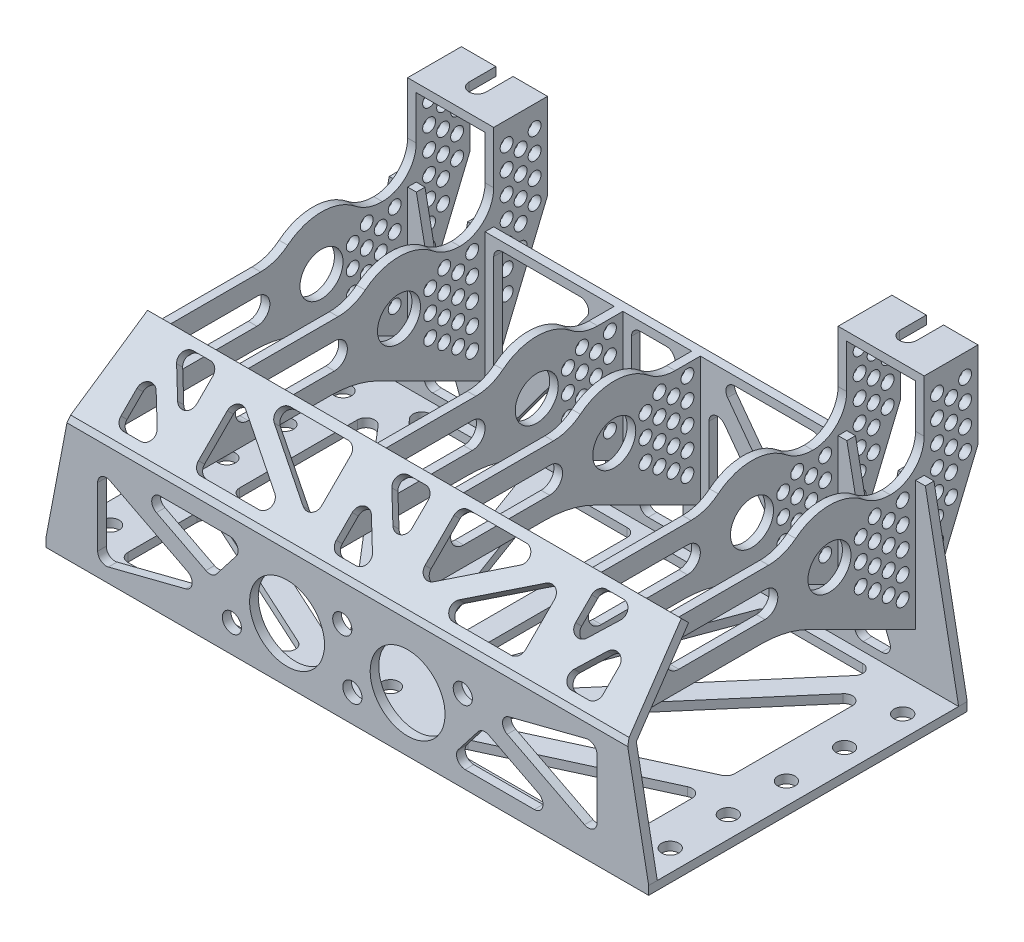
SolidWorks part; units mm, degrees
material "AISI 4340 Steel, normalized"
ref_plane "Front Plane" through (0, 0, 0) normal (0, 0, 1) x (1, 0, 0)
ref_plane "Top Plane" through (0, 0, 0) normal (0, 1, 0) x (1, 0, 0)
ref_plane "Right Plane" through (0, 0, 0) normal (1, 0, 0) x (0, 0, -1)
sketch "Sketch1" plane through (0, 0, 0) normal (1, 0, 0) x (0, 0, -1)
  line L0 (40, 15) -> (28.2843, 15)
  line L1 (-100, 15) -> (-100, -15)
  line L2 (-100, -15) -> (-31.8034, -15)
  line L3 (40, -15) -> (40, 15)
  line L4 (-28.2843, 15) -> (-100, 15)
  line L5 (-20, 15) -> (20, 15) construction
  line L6 (-9.4427, -20.2786) -> (40, -45)
  line L7 (40, -45) -> (40, -15)
  line L8 (-20, -15) -> (40, -15) construction
  line L9 (0, 0) -> (-100, 0) construction
  line L10 (-30, 0) -> (-60, 0) construction
  line L11 (-30, -6) -> (-60, -6)
  line L12 (-30, 6) -> (-60, 6)
  circle A0 centre (0, 0) radius 10
  arc A1 (-15.7135, 19.4444) -> (15.7135, 19.4444) centre (0, 0) cw
  arc A2 (15.7135, 19.4444) -> (28.2843, 15) centre (28.2843, 35) ccw
  arc A3 (-15.7135, 19.4444) -> (-28.2843, 15) centre (-28.2843, 35) cw
  arc A4 (-9.4427, -20.2786) -> (-31.8034, -15) centre (-31.8034, -65) ccw
  arc A5 (-30, -6) -> (-30, 6) centre (-30, 0) ccw
  arc A6 (-60, 6) -> (-60, -6) centre (-60, 0) ccw
  point P23 (-45, 0)
  dimension "D1" = 20
  dimension "D2" = 140
  dimension "D6" = 25
  dimension "D7" = 20
  dimension "D10" = 50
  dimension "D3" = 30
  dimension "D4" = 15
  dimension "D5" = 100
  dimension "D8" = 30
  dimension "D9" = 60
  dimension "D11" = 12
  dimension "D12" = 60
  dimension "D13" = 30
extrude "Boss-Extrude1" add sketch "Sketch1" along normal blind 4 from offset 16
mirror "Mirror1" about plane through (0, 0, 0) normal (1, 0, 0) of bodies 101
sketch "Sketch2" plane through (0, 0, 100) normal (0, 0, 1) x (1, 0, 0)
  line L0 (-140, 15) -> (140, 15)
  line L1 (140, 15) -> (140, -70)
  line L2 (140, -70) -> (-140, -70)
  line L3 (-140, -70) -> (-140, 15)
  dimension "D1" = 85
  dimension "D2" = 280
  dimension "D3" = 140
  dimension "D4" = 70
extrude "Boss-Extrude2" add sketch "Sketch2" along normal blind 4
sketch "Sketch3" plane through (0, 0, 104) normal (0, 0, 1) x (1, 0, 0)
  line L0 (0, 0) -> (0, -70) construction
  line L1 (-140, -70) -> (140, -70) construction
  circle A0 centre (-28, -44.5) radius 17.4
  circle A1 centre (28, -44.5) radius 17.4
  dimension "D4" = 34.8
  dimension "D5" = 28
  dimension "D6" = 44.5
extrude "Cut-Extrude1" cut sketch "Sketch3" against normal blind 10
sketch "Sketch4" plane through (0, 0, 104) normal (0, 0, 1) x (1, 0, 0)
  line L0 (-53.6437, -57.05) -> (-2.3563, -31.95) construction
  line L1 (2.3563, -57.05) -> (53.6437, -31.95) construction
  line L2 (0, 0) -> (0, -70) construction
  line L3 (-140, -70) -> (140, -70) construction
  line L4 (-28, -44.5) -> (28, -44.5) construction
  circle A8 centre (28, -44.5) radius 17.4 construction
  circle A9 centre (-28, -44.5) radius 17.4 construction
  circle A10 centre (28, -44.5) radius 17.4
  circle A11 centre (-28, -44.5) radius 17.4
  circle A12 centre (-28, -44.5) radius 28.55 construction
  circle A13 centre (28, -44.5) radius 28.55 construction
  circle A14 centre (-53.6437, -57.05) radius 4.45
  circle A15 centre (-2.3563, -31.95) radius 4.45
  circle A16 centre (2.3563, -57.05) radius 4.45
  circle A17 centre (53.6437, -31.95) radius 4.45
  dimension "D2" = 57.1
  dimension "D3" = 8.9
  dimension "D1" = 26.077
extrude "Cut-Extrude2" cut sketch "Sketch4" against normal blind 10
pattern_linear "LPattern2" count 2 spacing 64 along (1, 0, 0) count 2 spacing 100 along (-1, 0, 0) of "Boss-Extrude1"
sketch "Sketch5" plane through (84, 0, 0) normal (1, 0, 0) x (0, 0, -1)
  line L0 (-60, -6) -> (-30, -6) construction
  line L1 (-60, -6) -> (-30, -6)
  line L2 (-30, 6) -> (-60, 6) construction
  line L3 (-30, 6) -> (-60, 6)
  line L4 (40, -45) -> (40, 15)
  line L5 (40, 15) -> (28.2843, 15)
  line L6 (-100, 15) -> (-100, -15)
  line L7 (-100, -15) -> (-31.8034, -15)
  line L8 (40, -45) -> (40, 15)
  line L10 (-100, 15) -> (-100, -15)
  line L11 (-100, -15) -> (-31.8034, -15)
  line L14 (40, 15) -> (28.2843, 15)
  line L15 (-28.2843, 15) -> (-100, 15)
  line L16 (-28.2843, 15) -> (-100, 15)
  line L17 (-9.4427, -20.2786) -> (40, -45)
  line L18 (-9.4427, -20.2786) -> (40, -45)
  circle A0 centre (0, 0) radius 10 construction
  circle A1 centre (0, 0) radius 10
  arc A2 (-60, 6) -> (-60, -6) centre (-60, 0) ccw construction
  arc A3 (-30, -6) -> (-30, 6) centre (-30, 0) ccw construction
  arc A4 (-60, 6) -> (-60, -6) centre (-60, 0) ccw
  arc A5 (15.7135, 19.4444) -> (28.2843, 15) centre (28.2843, 35) ccw
  arc A6 (15.7135, 19.4444) -> (28.2843, 15) centre (28.2843, 35) ccw
  arc A7 (15.7135, 19.4444) -> (-15.7135, 19.4444) centre (0, 0) ccw
  arc A8 (15.7135, 19.4444) -> (-15.7135, 19.4444) centre (0, 0) ccw
  arc A9 (-28.2843, 15) -> (-15.7135, 19.4444) centre (-28.2843, 35) ccw
  arc A10 (-28.2843, 15) -> (-15.7135, 19.4444) centre (-28.2843, 35) ccw
  arc A11 (-30, -6) -> (-30, 6) centre (-30, 0) ccw
  arc A12 (-9.4427, -20.2786) -> (-31.8034, -15) centre (-31.8034, -65) ccw
  arc A13 (-9.4427, -20.2786) -> (-31.8034, -15) centre (-31.8034, -65) ccw
  dimension "D1" = 0
extrude "Boss-Extrude3" add sketch "Sketch5" along normal blind 4 from offset 32
sketch "Sketch6" plane through (-84, 0, 0) normal (-1, 0, 0) x (0, 0, 1)
  line L0 (30, 6) -> (60, 6) construction
  line L1 (60, -6) -> (30, -6) construction
  line L2 (30, 6) -> (60, 6)
  line L3 (60, -6) -> (30, -6)
  line L4 (-40, 15) -> (-40, -45)
  line L5 (31.8034, -15) -> (100, -15)
  line L6 (100, -15) -> (100, 15)
  line L7 (-28.2843, 15) -> (-40, 15)
  line L8 (-40, 15) -> (-40, -45)
  line L9 (31.8034, -15) -> (100, -15)
  line L10 (100, -15) -> (100, 15)
  line L11 (-28.2843, 15) -> (-40, 15)
  line L14 (-40, -45) -> (9.4427, -20.2786)
  line L15 (-40, -45) -> (9.4427, -20.2786)
  line L16 (100, 15) -> (28.2843, 15)
  line L17 (100, 15) -> (28.2843, 15)
  circle A0 centre (0, 0) radius 10 construction
  circle A1 centre (0, 0) radius 10
  arc A2 (30, 6) -> (30, -6) centre (30, 0) ccw construction
  arc A3 (60, -6) -> (60, 6) centre (60, 0) ccw construction
  arc A4 (30, 6) -> (30, -6) centre (30, 0) ccw
  arc A5 (15.7135, 19.4444) -> (28.2843, 15) centre (28.2843, 35) ccw
  arc A6 (15.7135, 19.4444) -> (28.2843, 15) centre (28.2843, 35) ccw
  arc A7 (15.7135, 19.4444) -> (-15.7135, 19.4444) centre (0, 0) ccw
  arc A8 (15.7135, 19.4444) -> (-15.7135, 19.4444) centre (0, 0) ccw
  arc A9 (-28.2843, 15) -> (-15.7135, 19.4444) centre (-28.2843, 35) ccw
  arc A10 (-28.2843, 15) -> (-15.7135, 19.4444) centre (-28.2843, 35) ccw
  arc A11 (60, -6) -> (60, 6) centre (60, 0) ccw
  arc A12 (31.8034, -15) -> (9.4427, -20.2786) centre (31.8034, -65) ccw
  arc A13 (31.8034, -15) -> (9.4427, -20.2786) centre (31.8034, -65) ccw
  dimension "D1" = 0
extrude "Boss-Extrude4" add sketch "Sketch6" along normal blind 4 from offset 32
sketch "Sketch7" plane through (0, 0, 0) normal (1, 0, 0) x (0, 0, -1)
  line L0 (-100, -15) -> (-70, 15)
  line L2 (-100, -15) -> (-31.8034, -15) construction
  line L3 (-70, 15) -> (-68.8914, 31.7021)
  line L4 (-68.8914, 31.7021) -> (-121.4755, 31.7021)
  line L5 (-121.4755, 31.7021) -> (-121.4755, -15)
  line L6 (-121.4755, -15) -> (-100, -15)
  line L7 (-28.2843, 15) -> (-100, 15) construction
  dimension "D1" = 45
extrude "Cut-Extrude3" cut sketch "Sketch7" against normal through all both and the other way through all
sketch "Sketch8" plane through (0, 0, 0) normal (1, 0, 0) x (0, 0, -1)
  line L0 (-100, -15) -> (-70, 15)
  line L1 (-102.8284, -12.1716) -> (-72.8284, 17.8284)
  line L2 (-100, -15) -> (-102.8284, -12.1716) construction
  line L3 (-72.8284, 17.8284) -> (-70, 15)
  line L4 (-104, -15) -> (-102.8284, -12.1716)
  line L5 (-100, -15) -> (-104, -15)
  line L6 (-28.2843, 15) -> (-70, 15) construction
  dimension "D1" = 4
extrude "Boss-Extrude5" add sketch "Sketch8" along normal mid plane 280
sketch "Sketch9" plane through (0, 0, -40) normal (0, 0, -1) x (-1, 0, 0)
  line L1 (-140, -70) -> (140, -70)
  line L2 (-140, -70) -> (-140, 15)
  line L3 (-140, 15) -> (140, 15)
  line L4 (140, -70) -> (140, 15)
  line L5 (0, 15) -> (0, -70) construction
  line L6 (-140, -27.5) -> (140, -27.5) construction
  point P0 (0, -27.5)
  dimension "D1" = 280
  dimension "D2" = 85
  dimension "D3" = 27.5
extrude "Boss-Extrude6" add sketch "Sketch9" along normal blind 4
sketch "Sketch10" plane through (0, -70, 0) normal (0, -1, 0) x (1, 0, 0)
  line L1 (-140, 104) -> (140, 104)
  line L2 (-140, 104) -> (-140, -44)
  line L3 (-140, -44) -> (140, -44)
  line L4 (140, 104) -> (140, -44)
extrude "Boss-Extrude7" add sketch "Sketch10" against normal blind 4
sketch "Sketch11" plane through (0, 45.3284, 45.3284) normal (0, 0.7071, 0.7071) x (1, 0, 0)
  line L0 (-140, -60.1041) -> (140, -60.1041) construction
  line L1 (-140, -38.8909) -> (-140, -81.3173) construction
  line L2 (140, -38.8909) -> (140, -81.3173) construction
  line L3 (0, -38.8909) -> (0, -81.3173) construction
  line L4 (140, -38.8909) -> (-140, -38.8909) construction
  line L5 (140, -81.3173) -> (-140, -81.3173) construction
  line L6 (-80, -38.8909) -> (-20, -81.3173) construction
  line L7 (-20, -81.3173) -> (-20, -38.8909) construction
  line L8 (-20, -9.3934) -> (-20, -38.8909) construction
  line L12 (-80, -38.8909) -> (-80, -81.3173) construction
  line L13 (-80, -81.3173) -> (-20, -81.3173) construction
  line L14 (-69.6906, -51.0797) -> (-42.8607, -70.0513)
  line L15 (-72, -77.3173) -> (-45.1701, -77.3173)
  line L16 (-76, -54.3457) -> (-76, -73.3173)
  line L17 (-80, -38.8909) -> (-20, -38.8909) construction
  line L18 (-57.1393, -50.1569) -> (-30.3094, -69.1285)
  line L19 (-24, -65.8625) -> (-24, -46.8909)
  line L20 (-54.8299, -42.8909) -> (-28, -42.8909)
  line L21 (-67.4149, -42.8909) -> (-24, -73.5899) construction
  line L22 (-67.4149, -42.8909) -> (-24, -42.8909) construction
  line L23 (-24, -73.5899) -> (-24, -42.8909) construction
  line L24 (-76, -46.6183) -> (-32.5851, -77.3173) construction
  line L25 (-76, -77.3173) -> (-32.5851, -77.3173) construction
  line L26 (-76, -46.6183) -> (-76, -77.3173) construction
  line L27 (76, -54.3457) -> (76, -73.3173)
  line L28 (69.6906, -51.0797) -> (42.8607, -70.0513)
  line L29 (72, -77.3173) -> (45.1701, -77.3173)
  line L30 (57.1393, -50.1569) -> (30.3094, -69.1285)
  line L31 (54.8299, -42.8909) -> (28, -42.8909)
  line L32 (24, -65.8625) -> (24, -46.8909)
  line L33 (-84, -38.8909) -> (-84, -81.3173) construction
  line L34 (-84, -81.3173) -> (-116, -38.8909) construction
  line L35 (-116, -38.8909) -> (-116, -81.3173) construction
  line L36 (-116, -81.3173) -> (-84, -81.3173) construction
  line L37 (-116, -38.8909) -> (-84, -38.8909) construction
  line L38 (-112, -62.7828) -> (-112, -73.3173)
  line L39 (-108, -77.3173) -> (-100.0544, -77.3173)
  line L40 (-96.8609, -70.9086) -> (-104.8065, -60.3741)
  line L41 (-88, -46.8909) -> (-88, -57.4253)
  line L42 (-95.1935, -59.834) -> (-103.1391, -49.2995)
  line L43 (-99.9456, -42.8909) -> (-92, -42.8909)
  line L44 (-112, -50.8368) -> (-112, -77.3173) construction
  line L45 (-112, -77.3173) -> (-92.0272, -77.3173) construction
  line L46 (-92.0272, -77.3173) -> (-112, -50.8368) construction
  line L47 (-88, -42.8909) -> (-88, -69.3713) construction
  line L48 (-88, -69.3713) -> (-107.9728, -42.8909) construction
  line L49 (-107.9728, -42.8909) -> (-88, -42.8909) construction
  line L50 (96.8609, -70.9086) -> (104.8065, -60.3741)
  line L51 (108, -77.3173) -> (100.0544, -77.3173)
  line L52 (112, -62.7828) -> (112, -73.3173)
  line L53 (95.1935, -59.834) -> (103.1391, -49.2995)
  line L54 (99.9456, -42.8909) -> (92, -42.8909)
  line L55 (88, -46.8909) -> (88, -57.4253)
  line L56 (12, -46.8909) -> (12, -57.4253)
  line L57 (4.8065, -59.834) -> (-3.1391, -49.2995)
  line L58 (0.0544, -42.8909) -> (8, -42.8909)
  line L59 (-12, -62.7828) -> (-12, -73.3173)
  line L60 (-8, -77.3173) -> (-0.0544, -77.3173)
  line L61 (3.1391, -70.9086) -> (-4.8065, -60.3741)
  arc A0 (-57.1393, -50.1569) -> (-54.8299, -42.8909) centre (-54.8299, -46.8909) cw
  arc A1 (-24, -46.8909) -> (-28, -42.8909) centre (-28, -46.8909) ccw
  arc A2 (-30.3094, -69.1285) -> (-24, -65.8625) centre (-28, -65.8625) ccw
  arc A3 (-42.8607, -70.0513) -> (-45.1701, -77.3173) centre (-45.1701, -73.3173) cw
  arc A4 (-72, -77.3173) -> (-76, -73.3173) centre (-72, -73.3173) cw
  arc A5 (-69.6906, -51.0797) -> (-76, -54.3457) centre (-72, -54.3457) ccw
  arc A6 (72, -77.3173) -> (76, -73.3173) centre (72, -73.3173) ccw
  arc A7 (69.6906, -51.0797) -> (76, -54.3457) centre (72, -54.3457) cw
  arc A8 (42.8607, -70.0513) -> (45.1701, -77.3173) centre (45.1701, -73.3173) ccw
  arc A9 (30.3094, -69.1285) -> (24, -65.8625) centre (28, -65.8625) cw
  arc A10 (57.1393, -50.1569) -> (54.8299, -42.8909) centre (54.8299, -46.8909) ccw
  arc A11 (24, -46.8909) -> (28, -42.8909) centre (28, -46.8909) cw
  arc A12 (-112, -73.3173) -> (-108, -77.3173) centre (-108, -73.3173) ccw
  arc A13 (-112, -62.7828) -> (-104.8065, -60.3741) centre (-108, -62.7828) cw
  arc A14 (-100.0544, -77.3173) -> (-96.8609, -70.9086) centre (-100.0544, -73.3173) ccw
  arc A15 (-88, -57.4253) -> (-95.1935, -59.834) centre (-92, -57.4253) cw
  arc A16 (-88, -46.8909) -> (-92, -42.8909) centre (-92, -46.8909) ccw
  arc A17 (-103.1391, -49.2995) -> (-99.9456, -42.8909) centre (-99.9456, -46.8909) cw
  arc A18 (100.0544, -77.3173) -> (96.8609, -70.9086) centre (100.0544, -73.3173) cw
  arc A19 (112, -73.3173) -> (108, -77.3173) centre (108, -73.3173) cw
  arc A20 (112, -62.7828) -> (104.8065, -60.3741) centre (108, -62.7828) ccw
  arc A21 (88, -57.4253) -> (95.1935, -59.834) centre (92, -57.4253) ccw
  arc A22 (103.1391, -49.2995) -> (99.9456, -42.8909) centre (99.9456, -46.8909) ccw
  arc A23 (88, -46.8909) -> (92, -42.8909) centre (92, -46.8909) cw
  arc A24 (12, -46.8909) -> (8, -42.8909) centre (8, -46.8909) ccw
  arc A25 (12, -57.4253) -> (4.8065, -59.834) centre (8, -57.4253) cw
  arc A26 (-3.1391, -49.2995) -> (0.0544, -42.8909) centre (0.0544, -46.8909) cw
  arc A27 (-12, -62.7828) -> (-4.8065, -60.3741) centre (-8, -62.7828) cw
  arc A28 (-12, -73.3173) -> (-8, -77.3173) centre (-8, -73.3173) ccw
  arc A29 (-0.0544, -77.3173) -> (3.1391, -70.9086) centre (-0.0544, -73.3173) ccw
  dimension "D3" = 4
  dimension "D6" = 4
  dimension "D1" = 4
  dimension "D2" = 4
  dimension "D4" = 4
  dimension "D5" = 4
  dimension "D7" = 2
extrude "Cut-Extrude4" cut sketch "Sketch11" against normal blind 4
sketch "Sketch12" plane through (0, 0, 104) normal (0, 0, 1) x (1, 0, 0)
  line L0 (0, -70) -> (0, 0) construction
  line L1 (-140, -70) -> (140, -70) construction
  line L2 (120, -15) -> (120, -66) construction
  line L3 (140, -66) -> (-140, -66) construction
  line L6 (61.655, -36.0609) -> (38.3935, -66) construction
  line L8 (42.5693, -55.8198) -> (58.3027, -35.5699) construction
  line L9 (120, -66) -> (61.655, -36.0609) construction
  line L19 (120, -70) -> (35.2856, -70) construction
  line L20 (53.6437, -31.95) -> (120, -15) construction
  line L21 (0, -43.705) -> (-140, -42.5) construction
  line L22 (-140, -15) -> (-140, -70) construction
  line L33 (140, -15) -> (-140, -15) construction
  line L37 (110.1738, -56.4619) -> (74.2598, -38.033)
  line L38 (75.096, -30.5987) -> (111.01, -21.4248)
  line L39 (116, -25.3004) -> (116, -52.9031)
  line L40 (120, -66) -> (53.6437, -31.95) construction
  line L41 (0, -66) -> (-140, -66) construction
  line L42 (86.8866, -62) -> (54.7401, -62)
  line L49 (120, -66) -> (38.3935, -66) construction
  line L50 (60.7446, -43.7522) -> (51.5814, -55.5458)
  line L51 (88.7128, -54.4412) -> (65.7295, -42.6476)
  line L52 (116, -59.4516) -> (64.8648, -33.2121) construction
  line L53 (116, -20.1502) -> (116, -59.4516) construction
  line L54 (64.8648, -33.2121) -> (116, -20.1502) construction
  line L55 (103.4433, -62) -> (46.5668, -62) construction
  line L56 (103.4433, -62) -> (62.7792, -41.1336) construction
  line L57 (62.7792, -41.1336) -> (46.5668, -62) construction
  line L58 (-86.8866, -22.8083) -> (-54.7401, -22.8083)
  line L59 (-60.7446, -41.0561) -> (-51.5814, -29.2624)
  line L60 (-88.7128, -30.3671) -> (-65.7295, -42.1607)
  line L61 (-110.1738, -28.3463) -> (-74.2598, -46.7752)
  line L62 (-75.096, -54.2096) -> (-111.01, -63.3834)
  line L63 (-116, -59.5079) -> (-116, -31.9052)
  arc A25 (110.1738, -56.4619) -> (116, -52.9031) centre (112, -52.9031) ccw
  arc A26 (111.01, -21.4248) -> (116, -25.3004) centre (112, -25.3004) cw
  arc A27 (86.8866, -62) -> (88.7128, -54.4412) centre (86.8866, -58) ccw
  arc A28 (60.7446, -43.7522) -> (65.7295, -42.6476) centre (63.9033, -46.2064) cw
  arc A29 (54.7401, -62) -> (51.5814, -55.5458) centre (54.7401, -58) cw
  arc A30 (74.2598, -38.033) -> (75.096, -30.5987) centre (76.086, -34.4742) cw
  arc A31 (-54.7401, -22.8083) -> (-51.5814, -29.2624) centre (-54.7401, -26.8083) cw
  arc A32 (-86.8866, -22.8083) -> (-88.7128, -30.3671) centre (-86.8866, -26.8083) ccw
  arc A33 (-60.7446, -41.0561) -> (-65.7295, -42.1607) centre (-63.9033, -38.6019) cw
  arc A34 (-74.2598, -46.7752) -> (-75.096, -54.2096) centre (-76.086, -50.334) cw
  arc A35 (-110.1738, -28.3463) -> (-116, -31.9052) centre (-112, -31.9052) ccw
  arc A36 (-111.01, -63.3834) -> (-116, -59.5079) centre (-112, -59.5079) cw
  point P62 (0, -42.775)
  point P69 (0, -42.4041)
  point P70 (0, -42.775)
  dimension "D5" = 2
  dimension "D4" = 4
  dimension "D3" = 4
  dimension "D1" = 35.2856
  dimension "D2" = 4
extrude "Cut-Extrude5" cut sketch "Sketch12" against normal blind 4
sketch "Sketch13" plane through (0, 0, -44) normal (0, 0, -1) x (-1, 0, 0)
  line L0 (0, 15) -> (0, -70) construction
  line L3 (-16, 15) -> (16, 15) construction
  line L4 (-140, -70) -> (140, -70) construction
  line L5 (-116, 15) -> (-116, -66) construction
  line L7 (-16, -66) -> (16, -66) construction
  line L8 (-84, 15) -> (-84, -66) construction
  line L9 (140, 15) -> (-140, 15) construction
  line L10 (-116, 15) -> (-84, 15) construction
  line L11 (-84, -66) -> (-116, 15) construction
  line L12 (-116, 15) -> (-84, 15) construction
  line L13 (-84, -66) -> (-116, -66) construction
  line L14 (-80, -66) -> (-20, -66) construction
  line L27 (-80, 15) -> (-80, -66) construction
  line L28 (-84, 15) -> (-80, 15) construction
  line L29 (-80, -66) -> (-20, 15) construction
  line L30 (-20, 15) -> (-20, -66) construction
  line L31 (-80, 15) -> (-20, 15) construction
  line L32 (-16, 15) -> (-16, -66) construction
  line L34 (-16, 15) -> (16, 15) construction
  line L35 (16, 15) -> (16, -66) construction
  line L36 (16, -66) -> (-16, 15) construction
  line L39 (-76, 7) -> (-76, -41.7598)
  line L40 (-68.7858, -44.1407) -> (-32.6674, 4.6191)
  line L41 (-72, 11) -> (-35.8817, 11)
  line L42 (-67.3326, -55.6191) -> (-31.2142, -6.8593)
  line L43 (-24, -9.2402) -> (-24, -58)
  line L44 (-64.1183, -62) -> (-28, -62)
  line L45 (-12, -27.023) -> (-12, -58)
  line L46 (-8, -62) -> (4.2378, -62)
  line L47 (7.958, -56.5303) -> (-4.2798, -25.5533)
  line L48 (4.2798, -25.4467) -> (-7.958, 5.5303)
  line L49 (-4.2378, 11) -> (8, 11)
  line L50 (12, 7) -> (12, -23.977)
  line L51 (-10.1189, 11) -> (12, 11) construction
  line L52 (12, 11) -> (12, -44.9885) construction
  line L53 (12, -44.9885) -> (-10.1189, 11) construction
  line L54 (-12, -62) -> (10.1189, -62) construction
  line L55 (10.1189, -62) -> (-12, -6.0115) construction
  line L56 (-12, -6.0115) -> (-12, -62) construction
  line L57 (-72.0592, -62) -> (-24, 2.8799) construction
  line L58 (-24, 2.8799) -> (-24, -62) construction
  line L59 (-72.0592, -62) -> (-24, -62) construction
  line L60 (-76, 11) -> (-76, -53.8799) construction
  line L61 (-76, -53.8799) -> (-27.9408, 11) construction
  line L62 (-76, 11) -> (-27.9408, 11) construction
  line L69 (80, 15) -> (20, 15) construction
  line L70 (20, 15) -> (20, -66) construction
  line L71 (80, -66) -> (20, 15) construction
  line L72 (80, 15) -> (80, -66) construction
  line L73 (80, -66) -> (20, -66) construction
  line L74 (84, -66) -> (116, -66) construction
  line L75 (116, 15) -> (84, 15) construction
  line L76 (84, -66) -> (116, 15) construction
  line L77 (84, 15) -> (84, -66) construction
  line L78 (116, 15) -> (116, -66) construction
  line L79 (64.1183, -62) -> (28, -62)
  line L80 (24, -9.2402) -> (24, -58)
  line L81 (67.3326, -55.6191) -> (31.2142, -6.8593)
  line L82 (72, 11) -> (35.8817, 11)
  line L83 (68.7858, -44.1407) -> (32.6674, 4.6191)
  line L84 (76, 7) -> (76, -41.7598)
  arc A0 (8, 11) -> (12, 7) centre (8, 7) cw
  arc A1 (-7.958, 5.5303) -> (-4.2378, 11) centre (-4.2378, 7) cw
  arc A2 (4.2798, -25.4467) -> (12, -23.977) centre (8, -23.977) ccw
  arc A3 (4.2378, -62) -> (7.958, -56.5303) centre (4.2378, -58) ccw
  arc A4 (-12, -58) -> (-8, -62) centre (-8, -58) ccw
  arc A5 (-12, -27.023) -> (-4.2798, -25.5533) centre (-8, -27.023) cw
  arc A6 (-31.2142, -6.8593) -> (-24, -9.2402) centre (-28, -9.2402) cw
  arc A7 (-24, -58) -> (-28, -62) centre (-28, -58) cw
  arc A8 (-67.3326, -55.6191) -> (-64.1183, -62) centre (-64.1183, -58) ccw
  arc A9 (-76, -41.7598) -> (-68.7858, -44.1407) centre (-72, -41.7598) ccw
  arc A10 (-32.6674, 4.6191) -> (-35.8817, 11) centre (-35.8817, 7) ccw
  arc A11 (-76, 7) -> (-72, 11) centre (-72, 7) cw
  arc A24 (76, 7) -> (72, 11) centre (72, 7) ccw
  arc A25 (32.6674, 4.6191) -> (35.8817, 11) centre (35.8817, 7) cw
  arc A26 (76, -41.7598) -> (68.7858, -44.1407) centre (72, -41.7598) cw
  arc A27 (67.3326, -55.6191) -> (64.1183, -62) centre (64.1183, -58) cw
  arc A28 (24, -58) -> (28, -62) centre (28, -58) ccw
  arc A29 (31.2142, -6.8593) -> (24, -9.2402) centre (28, -9.2402) ccw
  dimension "D5" = 4
  dimension "D8" = 4
  dimension "D1" = 4
  dimension "D4" = 4
  dimension "D6" = 4
  dimension "D7" = 4
extrude "Cut-Extrude6" cut sketch "Sketch13" against normal blind 4
sketch "Sketch14" plane through (0, -70, 0) normal (0, -1, 0) x (1, 0, 0)
  line L0 (0, -40) -> (0, 100) construction
  line L1 (-5, -31) -> (-5, 55.3142)
  line L2 (-10.8137, 56.355) -> (-42.6139, -29.6123)
  line L3 (-51.7876, -40) -> (0, -40) construction
  line L4 (-38.8624, -35) -> (-9, -35)
  line L6 (-120, 44.8095) -> (-120, 100) construction
  line L7 (-120, 100) -> (0, 100) construction
  line L8 (140, 100) -> (-140, 100) construction
  line L9 (-120, -40) -> (0, 100) construction
  line L10 (0, 100) -> (-120, 44.8095) construction
  line L11 (0, 100) -> (-51.7876, -40) construction
  line L23 (-39.4362, 87.3659) -> (-109.3286, 55.2209)
  line L24 (-120, 44.8095) -> (-120, -40) construction
  line L25 (-120, -40) -> (-51.7876, -40) construction
  line L26 (-115, 58.855) -> (-115, 91)
  line L27 (-111, 95) -> (-41.1076, 95)
  line L28 (-107.963, -18.2738) -> (-30.5473, 72.0444)
  line L29 (-35.2557, 78.2817) -> (-112.6714, 42.6766)
  line L30 (-115, 39.0425) -> (-115, -15.6707)
  line L31 (-20.1915, 59.8271) -> (-54.3028, -32.3877)
  line L32 (-100.432, -35) -> (-58.0544, -35)
  line L33 (-103.469, -28.3968) -> (-25.283, 62.8202)
  line L34 (-115, -26.4837) -> (-18.658, 85.9153) construction
  line L35 (-18.658, 85.9153) -> (-115, 41.6056) construction
  line L36 (-22.8375, 95) -> (-115, 52.6125) construction
  line L37 (-115, 95) -> (-22.8375, 95) construction
  line L38 (-5, -35) -> (-5, 72.0713) construction
  line L39 (-5, 72.0713) -> (-44.6069, -35) construction
  line L40 (-14.3783, 75.5424) -> (-55.2691, -35) construction
  line L41 (-109.1289, -35) -> (-14.3783, 75.5424) construction
  line L42 (-44.6069, -35) -> (-5, -35) construction
  line L43 (-109.1289, -35) -> (-55.2691, -35) construction
  line L44 (-115, 41.6056) -> (-115, -26.4837) construction
  line L45 (-115, 52.6125) -> (-115, 95) construction
  line L46 (38.8624, -35) -> (9, -35)
  line L47 (10.8137, 56.355) -> (42.6139, -29.6123)
  line L48 (5, -31) -> (5, 55.3142)
  line L49 (103.469, -28.3968) -> (25.283, 62.8202)
  line L50 (100.432, -35) -> (58.0544, -35)
  line L51 (20.1915, 59.8271) -> (54.3028, -32.3877)
  line L52 (115, 39.0425) -> (115, -15.6707)
  line L53 (35.2557, 78.2817) -> (112.6714, 42.6766)
  line L54 (107.963, -18.2738) -> (30.5473, 72.0444)
  line L55 (111, 95) -> (41.1076, 95)
  line L56 (115, 58.855) -> (115, 91)
  line L57 (39.4362, 87.3659) -> (109.3286, 55.2209)
  line L58 (-130, 104) -> (-130, -44) construction
  line L59 (-140, 104) -> (140, 104) construction
  line L60 (140, -44) -> (-140, -44) construction
  line L61 (130, 104) -> (130, -44) construction
  circle A24 centre (0, 100) radius 25 construction
  arc A25 (-30.5473, 72.0444) -> (-35.2557, 78.2817) centre (-33.5843, 74.6476) ccw
  arc A26 (-39.4362, 87.3659) -> (-41.1076, 95) centre (-41.1076, 91) ccw
  arc A27 (-5, 55.3142) -> (-10.8137, 56.355) centre (-8, 55.3142) ccw
  arc A28 (-20.1915, 59.8271) -> (-25.283, 62.8202) centre (-23.0052, 60.8679) ccw
  arc A29 (-5, -31) -> (-9, -35) centre (-9, -31) cw
  arc A30 (-42.6139, -29.6123) -> (-38.8624, -35) centre (-38.8624, -31) ccw
  arc A31 (-54.3028, -32.3877) -> (-58.0544, -35) centre (-58.0544, -31) cw
  arc A32 (-100.432, -35) -> (-103.469, -28.3968) centre (-100.432, -31) cw
  arc A33 (-107.963, -18.2738) -> (-115, -15.6707) centre (-111, -15.6707) cw
  arc A34 (-112.6714, 42.6766) -> (-115, 39.0425) centre (-111, 39.0425) ccw
  arc A35 (-109.3286, 55.2209) -> (-115, 58.855) centre (-111, 58.855) cw
  arc A36 (-115, 91) -> (-111, 95) centre (-111, 91) cw
  arc A37 (42.6139, -29.6123) -> (38.8624, -35) centre (38.8624, -31) cw
  arc A38 (5, 55.3142) -> (10.8137, 56.355) centre (8, 55.3142) cw
  arc A39 (5, -31) -> (9, -35) centre (9, -31) ccw
  arc A40 (100.432, -35) -> (103.469, -28.3968) centre (100.432, -31) ccw
  arc A41 (20.1915, 59.8271) -> (25.283, 62.8202) centre (23.0052, 60.8679) cw
  arc A42 (54.3028, -32.3877) -> (58.0544, -35) centre (58.0544, -31) ccw
  arc A43 (112.6714, 42.6766) -> (115, 39.0425) centre (111, 39.0425) cw
  arc A44 (30.5473, 72.0444) -> (35.2557, 78.2817) centre (33.5843, 74.6476) cw
  arc A45 (107.963, -18.2738) -> (115, -15.6707) centre (111, -15.6707) ccw
  arc A46 (115, 91) -> (111, 95) centre (111, 91) ccw
  arc A47 (39.4362, 87.3659) -> (41.1076, 95) centre (41.1076, 91) cw
  arc A48 (109.3286, 55.2209) -> (115, 58.855) centre (111, 58.855) ccw
  circle A49 centre (0, 84) radius 4
  circle A50 centre (-130, 84) radius 4
  circle A51 centre (-130, 57) radius 4
  circle A52 centre (-130, 30) radius 4
  circle A53 centre (-130, 3) radius 4
  circle A54 centre (-130, -24) radius 4
  circle A55 centre (130, -24) radius 4
  circle A56 centre (130, 3) radius 4
  circle A57 centre (130, 30) radius 4
  circle A58 centre (130, 57) radius 4
  circle A59 centre (130, 84) radius 4
  dimension "D10" = 4
  dimension "D2" = 50
  dimension "D8" = 4
  dimension "D9" = 3
  dimension "D11" = 16
  dimension "D12" = 8
  dimension "D14" = 8
  dimension "D17" = 20
  dimension "D1" = 5
  dimension "D3" = 20.3
  dimension "D4" = 24.7
  dimension "D5" = 5
  dimension "D13" = 130
  dimension "D15" = 20
  dimension "D6" = 5
  dimension "D7" = 5
  dimension "D16" = 5
extrude "Cut-Extrude7" cut sketch "Sketch14" against normal blind 4
sketch "Sketch15" plane through (0, 0, -44) normal (0, 0, -1) x (-1, 0, 0)
  line L0 (0, -70) -> (0, 15) construction
  line L1 (-140, -70) -> (140, -70) construction
  line L2 (140, 15) -> (-140, 15) construction
  line L3 (-100, 15) -> (-100, -70) construction
  line L4 (-116, 15) -> (-84, 15) construction
  line L5 (-116, 15) -> (-116, -70) construction
  line L6 (-84, 15) -> (-84, -70) construction
  line L7 (-116, -66) -> (-84, -66) construction
  line L8 (-116, 15) -> (-100, -66) construction
  line L9 (-100, -66) -> (-84, 15) construction
  line L10 (-84, 15) -> (-116, 15) construction
  line L11 (-112.0758, 15.7751) -> (-103.9242, -25.4926)
  line L12 (-96.0758, -25.4926) -> (-87.9242, 15.7751)
  line L13 (-112.0758, 15.7751) -> (-87.9242, 15.7751)
  line L14 (-112.0758, 15.7751) -> (-100, -45.3587) construction
  line L15 (-100, -45.3587) -> (-87.9242, 15.7751) construction
  line L16 (-84, -66) -> (-100, -24.7174) construction
  line L17 (-100, -24.7174) -> (-116, -66) construction
  line L18 (-116, -66) -> (-84, -66) construction
  line L19 (-104.3196, -62) -> (-95.6804, -62)
  line L20 (-91.9507, -56.5545) -> (-96.2703, -45.4093)
  line L21 (-103.7297, -45.4093) -> (-108.0493, -56.5545)
  line L22 (-110.1598, -62) -> (-89.8402, -62) construction
  line L23 (-89.8402, -62) -> (-100, -35.7861) construction
  line L24 (-100, -35.7861) -> (-110.1598, -62) construction
  line L25 (103.7297, -45.4093) -> (108.0493, -56.5545)
  line L26 (91.9507, -56.5545) -> (96.2703, -45.4093)
  line L27 (104.3196, -62) -> (95.6804, -62)
  line L28 (112.0758, 15.7751) -> (103.9242, -25.4926)
  line L29 (96.0758, -25.4926) -> (87.9242, 15.7751)
  line L30 (112.0758, 15.7751) -> (87.9242, 15.7751)
  arc A0 (-103.9242, -25.4926) -> (-96.0758, -25.4926) centre (-100, -24.7174) ccw
  arc A1 (-95.6804, -62) -> (-91.9507, -56.5545) centre (-95.6804, -58) ccw
  arc A2 (-104.3196, -62) -> (-108.0493, -56.5545) centre (-104.3196, -58) cw
  arc A3 (-96.2703, -45.4093) -> (-103.7297, -45.4093) centre (-100, -46.8548) ccw
  arc A4 (96.2703, -45.4093) -> (103.7297, -45.4093) centre (100, -46.8548) cw
  arc A5 (95.6804, -62) -> (91.9507, -56.5545) centre (95.6804, -58) cw
  arc A6 (104.3196, -62) -> (108.0493, -56.5545) centre (104.3196, -58) ccw
  arc A7 (103.9242, -25.4926) -> (96.0758, -25.4926) centre (100, -24.7174) cw
  dimension "D2" = 4
  dimension "D4" = 4
  dimension "D1" = 4
  dimension "D3" = 4
extrude "Cut-Extrude8" cut sketch "Sketch15" against normal blind 10
sketch "Sketch16" plane through (0, 0, 0) normal (1, 0, 0) x (0, 0, -1)
  line L0 (44, 30.7157) -> (44, 55)
  line L1 (44, 55) -> (69, 55)
  line L2 (69, 55) -> (69, 15)
  line L3 (69, 15) -> (44, -45)
  line L4 (44, 15) -> (44, -70) construction
  line L5 (44, -45) -> (44, 15)
  line L6 (50, 55) -> (50, -30.6) construction
  line L7 (56.5, 55) -> (56.5, -15) construction
  line L8 (63, 55) -> (63, -30.6) construction
  line L9 (44, 15) -> (28.2843, 15)
  line L10 (44, 15) -> (44, 30.7157) construction
  circle A0 centre (50, 45) radius 3
  circle A1 centre (50, 35) radius 3
  circle A2 centre (50, 25) radius 3
  circle A3 centre (50, 15) radius 3
  circle A4 centre (50, 5) radius 3
  circle A5 centre (50, -5) radius 3
  circle A6 centre (50, -15) radius 3
  circle A7 centre (56.5, 40) radius 3
  circle A8 centre (56.5, 30) radius 3
  circle A9 centre (56.5, 20) radius 3
  circle A10 centre (56.5, 10) radius 3
  circle A11 centre (56.5, 0) radius 3
  circle A12 centre (63, 15) radius 3
  circle A13 centre (63, 25) radius 3
  circle A14 centre (63, 35) radius 3
  circle A15 centre (63, 45) radius 3
  arc A16 (28.2843, 15) -> (44, 30.7157) centre (28.2843, 30.7157) ccw
  dimension "D4" = 6
  dimension "D8" = 10
  dimension "D9" = 6
  dimension "D12" = 10
  dimension "D1" = 25
  dimension "D2" = 60
  dimension "D3" = 40
  dimension "D5" = 6
  dimension "D6" = 10
  dimension "D10" = 5
  dimension "D7" = 7
  dimension "D11" = 5
extrude "Boss-Extrude8" add sketch "Sketch16" along normal blind 4 from offset 80
pattern_linear "LPattern3" count 2 spacing 36 along (1, 0, 0) of "Boss-Extrude8"
sketch "Sketch17" plane through (0, 55, 0) normal (0, 1, 0) x (1, 0, 0)
  line L0 (80, 56.5) -> (120, 56.5) construction
  line L1 (80, 69) -> (96, 69)
  line L2 (80, 69) -> (80, 44)
  line L3 (80, 44) -> (120, 44)
  line L4 (120, 69) -> (120, 44)
  line L5 (104, 56.5) -> (104, 69)
  line L6 (96, 56.5) -> (96, 69)
  line L7 (104, 69) -> (120, 69)
  arc A0 (96, 56.5) -> (104, 56.5) centre (100, 56.5) ccw
  dimension "D1" = 8
extrude "Boss-Extrude9" add sketch "Sketch17" against normal blind 4
mirror "Mirror2" about plane through (0, 0, 0) normal (1, 0, 0) of "Boss-Extrude9", "LPattern3", "Boss-Extrude8"
sketch "Sketch18" plane through (0, 0, 0) normal (1, 0, 0) x (0, 0, -1)
  line L0 (40, 15) -> (40, -66) construction
  line L1 (-9.4427, -20.2786) -> (40, -45) construction
  line L2 (40, 15) -> (40, -66)
  line L3 (-9.4427, -20.2786) -> (40, -45)
  line L4 (34, -49.1) -> (34, 39.0052) construction
  line L5 (27.5, 17.2341) -> (27.5, -44.0387) construction
  line L6 (21, -49.1) -> (21, 39.0052) construction
  line L7 (-60, -6) -> (-30, -6) construction
  line L8 (-30, 6) -> (-60, 6) construction
  line L9 (-60, -6) -> (-30, -6)
  line L10 (-30, 6) -> (-60, 6)
  line L11 (-60, 6) -> (-70, 6)
  line L12 (-60, -6) -> (-70, -6)
  arc A0 (15.7135, 19.4444) -> (28.2843, 15) centre (28.2843, 35) ccw construction
  arc A1 (28.2843, 15) -> (44, 30.7157) centre (28.2843, 30.7157) ccw construction
  circle A2 centre (0, 0) radius 10 construction
  arc A3 (15.7135, 19.4444) -> (28.2843, 15) centre (28.2843, 35) ccw
  arc A4 (28.2843, 15) -> (44, 30.7157) centre (28.2843, 30.7157) ccw
  circle A5 centre (0, 0) radius 10
  circle A6 centre (34, 10) radius 3
  circle A7 centre (34, 0) radius 3
  circle A8 centre (34, -10) radius 3
  circle A9 centre (34, -20) radius 3
  circle A10 centre (34, -30) radius 3
  circle A11 centre (27.5, 5) radius 3
  circle A12 centre (27.5, -5) radius 3
  circle A13 centre (27.5, -15) radius 3
  circle A14 centre (27.5, -25) radius 3
  circle A15 centre (21, -20) radius 3
  circle A16 centre (21, -10) radius 3
  circle A17 centre (21, 0) radius 3
  circle A18 centre (21, 10) radius 3
  circle A19 centre (14.5, -15) radius 3
  circle A20 centre (14.5, -5) radius 3
  circle A21 centre (14.5, 5) radius 3
  arc A22 (-30, -6) -> (-30, 6) centre (-30, 0) ccw construction
  arc A23 (-30, -6) -> (-30, 6) centre (-30, 0) ccw
  arc A24 (-70, 6) -> (-70, -6) centre (-70, 0) ccw
  dimension "D2" = 6
  dimension "D5" = 40
  dimension "D7" = 5
  dimension "D9" = 30
  dimension "D10" = 12
  dimension "D1" = 6
  dimension "D3" = 5
  dimension "D6" = 6.5
  dimension "D11" = 40
  dimension "D4" = 5
  dimension "D8" = 4
extrude "Cut-Extrude9" cut sketch "Sketch18" against normal through all both and the other way through all contours L11 A24 L12 L9 A23 L10 | A11 | A15 | A18 | A6 | A7 | A8 | A12 | A17 | A21 | A20 | A16 | A13 | A9 | A10 | A14 | A19
sketch "Sketch19" plane through (0, 0, 0) normal (0, 0, 1) x (1, 0, 0)
  line L0 (-140, -66) -> (140, -66) construction
  line L1 (140, -70) -> (140, -15) construction
  line L2 (0, -66) -> (0, 0) construction
  line L3 (124, 17.8284) -> (120, 17.8284) construction
  line L4 (140, 17.8284) -> (-140, 17.8284) construction
  line L5 (124, 17.8284) -> (140, -66)
  line L6 (120, 15) -> (120, 55) construction
  line L7 (140, -66) -> (144, -66)
  line L8 (144, -66) -> (144, 21.8284)
  line L9 (144, 21.8284) -> (124, 21.8284)
  line L10 (124, 21.8284) -> (124, 17.8284)
  line L11 (-144, 21.8284) -> (-124, 21.8284)
  line L12 (-144, -66) -> (-144, 21.8284)
  line L13 (-140, -66) -> (-144, -66)
  line L14 (-124, 17.8284) -> (-140, -66)
  line L15 (-124, 21.8284) -> (-124, 17.8284)
  dimension "D1" = 4
  dimension "D2" = 4
  dimension "D3" = 4
extrude "Cut-Extrude10" cut sketch "Sketch19" against normal through all both and the other way through all
sketch "Sketch21" plane through (120, 0, 0) normal (1, 0, 0) x (0, 0, -1)
  line L0 (-30, 6) -> (-70, 6) construction
  line L1 (-70, -6) -> (-30, -6) construction
  line L2 (-30, 6) -> (-70, 6)
  line L3 (-70, -6) -> (-30, -6)
  line L11 (44, 55) -> (44, 30.7157)
  line L12 (-28.2843, 15) -> (-70, 15)
  line L13 (-70, 15) -> (-100, -15)
  line L14 (-100, -15) -> (-31.8034, -15)
  line L15 (-9.4427, -20.2786) -> (40, -45)
  line L16 (40, -45) -> (40, 15)
  line L17 (40, 15) -> (44, 15)
  line L18 (44, 15) -> (44, -45)
  line L19 (44, -45) -> (69, 15)
  line L20 (69, 15) -> (69, 55)
  line L21 (69, 55) -> (44, 55)
  line L22 (44, 55) -> (44, 30.7157)
  line L23 (-28.2843, 15) -> (-70, 15)
  line L24 (-70, 15) -> (-100, -15)
  line L25 (-100, -15) -> (-31.8034, -15)
  line L26 (-9.4427, -20.2786) -> (40, -45)
  line L27 (40, -45) -> (40, 15)
  line L28 (40, 15) -> (44, 15)
  line L29 (44, 15) -> (44, -45)
  line L30 (44, -45) -> (69, 15)
  line L31 (69, 15) -> (69, 55)
  line L32 (69, 55) -> (44, 55)
  circle A0 centre (0, 0) radius 10 construction
  arc A1 (-30, -6) -> (-30, 6) centre (-30, 0) ccw construction
  arc A2 (-70, 6) -> (-70, -6) centre (-70, 0) ccw construction
  circle A3 centre (0, 0) radius 10
  arc A4 (-30, -6) -> (-30, 6) centre (-30, 0) ccw
  arc A5 (28.2843, 15) -> (44, 30.7157) centre (28.2843, 30.7157) ccw
  arc A6 (15.7135, 19.4444) -> (28.2843, 15) centre (28.2843, 35) ccw
  arc A7 (15.7135, 19.4444) -> (-15.7135, 19.4444) centre (0, 0) ccw
  arc A8 (-28.2843, 15) -> (-15.7135, 19.4444) centre (-28.2843, 35) ccw
  arc A9 (-9.4427, -20.2786) -> (-31.8034, -15) centre (-31.8034, -65) ccw
  arc A10 (28.2843, 15) -> (44, 30.7157) centre (28.2843, 30.7157) ccw
  arc A11 (15.7135, 19.4444) -> (28.2843, 15) centre (28.2843, 35) ccw
  arc A12 (15.7135, 19.4444) -> (-15.7135, 19.4444) centre (0, 0) ccw
  arc A13 (-28.2843, 15) -> (-15.7135, 19.4444) centre (-28.2843, 35) ccw
  arc A14 (-9.4427, -20.2786) -> (-31.8034, -15) centre (-31.8034, -65) ccw
  arc A15 (-70, 6) -> (-70, -6) centre (-70, 0) ccw
  circle A16 centre (56.5, 0) radius 3 construction
  circle A17 centre (56.5, 10) radius 3 construction
  circle A18 centre (63, 15) radius 3 construction
  circle A19 centre (56.5, 20) radius 3 construction
  circle A20 centre (63, 25) radius 3 construction
  circle A21 centre (56.5, 30) radius 3 construction
  circle A22 centre (63, 35) radius 3 construction
  circle A23 centre (63, 45) radius 3 construction
  circle A24 centre (56.5, 40) radius 3 construction
  circle A25 centre (50, 45) radius 3 construction
  circle A26 centre (50, 35) radius 3 construction
  circle A27 centre (50, 25) radius 3 construction
  circle A28 centre (50, 15) radius 3 construction
  circle A29 centre (50, 5) radius 3 construction
  circle A30 centre (50, -5) radius 3 construction
  circle A31 centre (50, -15) radius 3 construction
  circle A32 centre (34, 10) radius 3 construction
  circle A33 centre (34, 0) radius 3 construction
  circle A34 centre (27.5, 5) radius 3 construction
  circle A35 centre (21, 10) radius 3 construction
  circle A36 centre (21, 0) radius 3 construction
  circle A37 centre (27.5, -5) radius 3 construction
  circle A38 centre (34, -10) radius 3 construction
  circle A39 centre (21, -10) radius 3 construction
  circle A40 centre (27.5, -15) radius 3 construction
  circle A41 centre (34, -20) radius 3 construction
  circle A42 centre (34, -30) radius 3 construction
  circle A43 centre (27.5, -25) radius 3 construction
  circle A44 centre (21, -20) radius 3 construction
  circle A45 centre (14.5, -15) radius 3 construction
  circle A46 centre (56.5, 0) radius 3
  circle A47 centre (56.5, 10) radius 3
  circle A48 centre (63, 15) radius 3
  circle A49 centre (56.5, 20) radius 3
  circle A50 centre (63, 25) radius 3
  circle A51 centre (56.5, 30) radius 3
  circle A52 centre (63, 35) radius 3
  circle A53 centre (63, 45) radius 3
  circle A54 centre (56.5, 40) radius 3
  circle A55 centre (50, 45) radius 3
  circle A56 centre (50, 35) radius 3
  circle A57 centre (50, 25) radius 3
  circle A58 centre (50, 15) radius 3
  circle A59 centre (50, 5) radius 3
  circle A60 centre (50, -5) radius 3
  circle A61 centre (50, -15) radius 3
  circle A62 centre (34, 10) radius 3
  circle A63 centre (34, 0) radius 3
  circle A64 centre (27.5, 5) radius 3
  circle A65 centre (21, 10) radius 3
  circle A66 centre (21, 0) radius 3
  circle A67 centre (27.5, -5) radius 3
  circle A68 centre (34, -10) radius 3
  circle A69 centre (21, -10) radius 3
  circle A70 centre (27.5, -15) radius 3
  circle A71 centre (34, -20) radius 3
  circle A72 centre (34, -30) radius 3
  circle A73 centre (27.5, -25) radius 3
  circle A74 centre (21, -20) radius 3
  circle A75 centre (14.5, -15) radius 3
  dimension "D1" = 0
sketch "Sketch22" plane through (0, -70, 0) normal (0, -1, 0) x (1, 0, 0)
  line L0 (-109.3286, 55.2209) -> (-39.4362, 87.3659) construction
  line L1 (-115, 91) -> (-115, 58.855) construction
  line L2 (-41.1076, 95) -> (-111, 95) construction
  line L3 (-109.3286, 55.2209) -> (-39.4362, 87.3659)
  line L4 (-140, 104) -> (-140, -44)
  line L5 (-140, -44) -> (140, -44)
  line L6 (140, -44) -> (140, 104)
  line L7 (140, 104) -> (-140, 104)
  line L8 (-140, 104) -> (-140, -44)
  line L9 (-140, -44) -> (140, -44)
  line L10 (140, -44) -> (140, 104)
  line L12 (-115, 91) -> (-115, 58.855)
  line L13 (-41.1076, 95) -> (-111, 95)
  line L14 (-107.963, -18.2738) -> (-30.5473, 72.0444) construction
  line L15 (-35.2557, 78.2817) -> (-112.6714, 42.6766) construction
  line L16 (-115, 39.0425) -> (-115, -15.6707) construction
  line L17 (-115, 39.0425) -> (-115, -15.6707)
  line L18 (-35.2557, 78.2817) -> (-112.6714, 42.6766)
  line L19 (-107.963, -18.2738) -> (-30.5473, 72.0444)
  line L20 (-100.432, -35) -> (-58.0544, -35) construction
  line L21 (-54.3028, -32.3877) -> (-20.1915, 59.8271) construction
  line L22 (-25.283, 62.8202) -> (-103.469, -28.3968) construction
  line L23 (-100.432, -35) -> (-58.0544, -35)
  line L24 (-54.3028, -32.3877) -> (-20.1915, 59.8271)
  line L25 (-25.283, 62.8202) -> (-103.469, -28.3968)
  line L26 (-5, -31) -> (-5, 55.3142) construction
  line L27 (-10.8137, 56.355) -> (-42.6139, -29.6123) construction
  line L28 (-38.8624, -35) -> (-9, -35) construction
  line L29 (-38.8624, -35) -> (-9, -35)
  line L30 (-10.8137, 56.355) -> (-42.6139, -29.6123)
  line L31 (-5, -31) -> (-5, 55.3142)
  line L32 (9, -35) -> (38.8624, -35) construction
  line L33 (5, 55.3142) -> (5, -31) construction
  line L34 (42.6139, -29.6123) -> (10.8137, 56.355) construction
  line L35 (9, -35) -> (38.8624, -35)
  line L36 (5, 55.3142) -> (5, -31)
  line L37 (42.6139, -29.6123) -> (10.8137, 56.355)
  line L38 (115, 58.855) -> (115, 91) construction
  line L39 (39.4362, 87.3659) -> (109.3286, 55.2209) construction
  line L40 (111, 95) -> (41.1076, 95) construction
  line L41 (112.6714, 42.6766) -> (35.2557, 78.2817) construction
  line L42 (115, -15.6707) -> (115, 39.0425) construction
  line L43 (30.5473, 72.0444) -> (107.963, -18.2738) construction
  line L44 (58.0544, -35) -> (100.432, -35) construction
  line L45 (20.1915, 59.8271) -> (54.3028, -32.3877) construction
  line L46 (103.469, -28.3968) -> (25.283, 62.8202) construction
  line L47 (115, 58.855) -> (115, 91)
  line L48 (39.4362, 87.3659) -> (109.3286, 55.2209)
  line L49 (111, 95) -> (41.1076, 95)
  line L50 (112.6714, 42.6766) -> (35.2557, 78.2817)
  line L51 (115, -15.6707) -> (115, 39.0425)
  line L52 (30.5473, 72.0444) -> (107.963, -18.2738)
  line L53 (58.0544, -35) -> (100.432, -35)
  line L54 (20.1915, 59.8271) -> (54.3028, -32.3877)
  line L55 (103.469, -28.3968) -> (25.283, 62.8202)
  line L56 (-140, 104) -> (140, 104) construction
  line L57 (-140, 104) -> (140, 104)
  circle A0 centre (-130, 84) radius 4 construction
  circle A1 centre (-130, 57) radius 4 construction
  circle A2 centre (-130, 30) radius 4 construction
  circle A3 centre (-130, 3) radius 4 construction
  circle A4 centre (0, 84) radius 4 construction
  circle A5 centre (130, 84) radius 4 construction
  circle A6 centre (130, 57) radius 4 construction
  circle A7 centre (130, 30) radius 4 construction
  circle A8 centre (130, 3) radius 4 construction
  circle A9 centre (130, -24) radius 4 construction
  circle A10 centre (-130, -24) radius 4 construction
  circle A11 centre (0, 84) radius 4
  circle A12 centre (130, 84) radius 4
  circle A13 centre (130, 57) radius 4
  circle A14 centre (130, 30) radius 4
  circle A15 centre (130, 3) radius 4
  circle A16 centre (130, -24) radius 4
  circle A17 centre (-130, -24) radius 4
  circle A18 centre (-130, 3) radius 4
  circle A19 centre (-130, 30) radius 4
  circle A20 centre (-130, 57) radius 4
  circle A21 centre (-130, 84) radius 4
  arc A22 (-39.4362, 87.3659) -> (-41.1076, 95) centre (-41.1076, 91) ccw construction
  arc A23 (-115, 58.855) -> (-109.3286, 55.2209) centre (-111, 58.855) ccw construction
  arc A24 (-111, 95) -> (-115, 91) centre (-111, 91) ccw construction
  arc A25 (-39.4362, 87.3659) -> (-41.1076, 95) centre (-41.1076, 91) ccw
  arc A26 (-115, 58.855) -> (-109.3286, 55.2209) centre (-111, 58.855) ccw
  arc A27 (-111, 95) -> (-115, 91) centre (-111, 91) ccw
  arc A28 (-30.5473, 72.0444) -> (-35.2557, 78.2817) centre (-33.5843, 74.6476) ccw construction
  arc A29 (-115, -15.6707) -> (-107.963, -18.2738) centre (-111, -15.6707) ccw construction
  arc A30 (-115, -15.6707) -> (-107.963, -18.2738) centre (-111, -15.6707) ccw
  arc A31 (-30.5473, 72.0444) -> (-35.2557, 78.2817) centre (-33.5843, 74.6476) ccw
  arc A32 (-103.469, -28.3968) -> (-100.432, -35) centre (-100.432, -31) ccw construction
  arc A33 (-58.0544, -35) -> (-54.3028, -32.3877) centre (-58.0544, -31) ccw construction
  arc A34 (-20.1915, 59.8271) -> (-25.283, 62.8202) centre (-23.0052, 60.8679) ccw construction
  arc A35 (-103.469, -28.3968) -> (-100.432, -35) centre (-100.432, -31) ccw
  arc A36 (-58.0544, -35) -> (-54.3028, -32.3877) centre (-58.0544, -31) ccw
  arc A37 (-20.1915, 59.8271) -> (-25.283, 62.8202) centre (-23.0052, 60.8679) ccw
  arc A38 (-5, 55.3142) -> (-10.8137, 56.355) centre (-8, 55.3142) ccw construction
  arc A39 (-42.6139, -29.6123) -> (-38.8624, -35) centre (-38.8624, -31) ccw construction
  arc A40 (-9, -35) -> (-5, -31) centre (-9, -31) ccw construction
  arc A41 (-9, -35) -> (-5, -31) centre (-9, -31) ccw
  arc A42 (-42.6139, -29.6123) -> (-38.8624, -35) centre (-38.8624, -31) ccw
  arc A43 (-5, 55.3142) -> (-10.8137, 56.355) centre (-8, 55.3142) ccw
  arc A44 (38.8624, -35) -> (42.6139, -29.6123) centre (38.8624, -31) ccw construction
  arc A45 (5, -31) -> (9, -35) centre (9, -31) ccw construction
  arc A46 (10.8137, 56.355) -> (5, 55.3142) centre (8, 55.3142) ccw construction
  arc A47 (38.8624, -35) -> (42.6139, -29.6123) centre (38.8624, -31) ccw
  arc A48 (5, -31) -> (9, -35) centre (9, -31) ccw
  arc A49 (10.8137, 56.355) -> (5, 55.3142) centre (8, 55.3142) ccw
  arc A50 (109.3286, 55.2209) -> (115, 58.855) centre (111, 58.855) ccw construction
  arc A51 (115, 91) -> (111, 95) centre (111, 91) ccw construction
  arc A52 (41.1076, 95) -> (39.4362, 87.3659) centre (41.1076, 91) ccw construction
  arc A53 (35.2557, 78.2817) -> (30.5473, 72.0444) centre (33.5843, 74.6476) ccw construction
  arc A54 (115, 39.0425) -> (112.6714, 42.6766) centre (111, 39.0425) ccw construction
  arc A55 (107.963, -18.2738) -> (115, -15.6707) centre (111, -15.6707) ccw construction
  arc A56 (100.432, -35) -> (103.469, -28.3968) centre (100.432, -31) ccw construction
  arc A57 (54.3028, -32.3877) -> (58.0544, -35) centre (58.0544, -31) ccw construction
  arc A58 (25.283, 62.8202) -> (20.1915, 59.8271) centre (23.0052, 60.8679) ccw construction
  arc A59 (109.3286, 55.2209) -> (115, 58.855) centre (111, 58.855) ccw
  arc A60 (115, 91) -> (111, 95) centre (111, 91) ccw
  arc A61 (41.1076, 95) -> (39.4362, 87.3659) centre (41.1076, 91) ccw
  arc A62 (35.2557, 78.2817) -> (30.5473, 72.0444) centre (33.5843, 74.6476) ccw
  arc A63 (115, 39.0425) -> (112.6714, 42.6766) centre (111, 39.0425) ccw
  arc A64 (107.963, -18.2738) -> (115, -15.6707) centre (111, -15.6707) ccw
  arc A65 (100.432, -35) -> (103.469, -28.3968) centre (100.432, -31) ccw
  arc A66 (54.3028, -32.3877) -> (58.0544, -35) centre (58.0544, -31) ccw
  arc A67 (25.283, 62.8202) -> (20.1915, 59.8271) centre (23.0052, 60.8679) ccw
  dimension "D1" = 0
